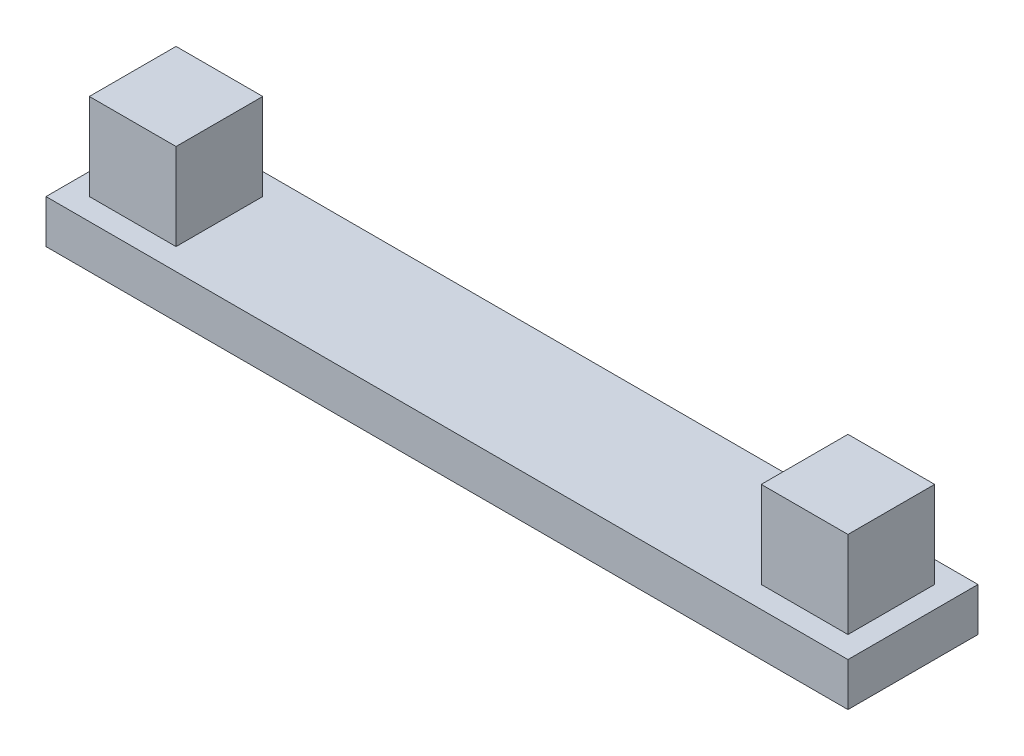
SolidWorks part; units mm, degrees
ref_plane "Front Plane" through (0, 0, 0) normal (0, 0, 1) x (1, 0, 0)
ref_plane "Top Plane" through (0, 0, 0) normal (0, 1, 0) x (1, 0, 0)
ref_plane "Right Plane" through (0, 0, 0) normal (1, 0, 0) x (0, 0, -1)
sketch "Sketch1" plane through (0, 0, 0) normal (0, 1, 0) x (1, 0, 0)
  line L1 (0, 0) -> (18.5, 0)
  line L2 (0, 0) -> (0, 3)
  line L3 (0, 3) -> (18.5, 3)
  line L4 (18.5, 0) -> (18.5, 3)
  line L5 (0, 0) -> (18.5, 3) construction
  line L6 (0, 3) -> (18.5, 0) construction
  line L7 (0.5, 2.5) -> (2.5, 2.5)
  line L8 (0.5, 2.5) -> (0.5, 0.5)
  line L9 (0.5, 0.5) -> (2.5, 0.5)
  line L10 (2.5, 2.5) -> (2.5, 0.5)
  line L11 (0.5, 2.5) -> (2.5, 0.5) construction
  line L12 (0.5, 0.5) -> (2.5, 2.5) construction
  line L13 (16, 2.5) -> (18, 2.5)
  line L14 (16, 2.5) -> (16, 0.5)
  line L15 (16, 0.5) -> (18, 0.5)
  line L16 (18, 2.5) -> (18, 0.5)
  line L17 (16, 2.5) -> (18, 0.5) construction
  line L18 (16, 0.5) -> (18, 2.5) construction
  point P4 (9.25, 1.5)
  point P10 (1.5, 1.5)
  point P15 (17, 1.5)
  point P16 (0, 0)
  point P17 (0, 1.5)
  point P18 (0, 0)
  point P19 (0, 0)
  point P20 (0, 0)
  point P21 (0, 0)
  point P22 (18.5, 1.5)
  dimension "D1" = 18.5
  dimension "D2" = 3
  dimension "D3" = 15.5
  dimension "D4" = 2
  dimension "D5" = 7.75
extrude "Boss-Extrude1" add sketch "Sketch1" along normal blind 1 contours L1 L4 L3 L2 L7 L10 L9 L8 L13 L16 L15 L14 region at (9.25, 0, -1.5)
ref_plane "Plane1" through (2.5, 0, -2.5) normal (1, 0, 0) x (0, 0, -1)
extrude "Boss-Extrude2" add sketch "Sketch1<3>" along normal blind 3 contours L7 L10 L9 L8 | L13 L16 L15 L14
sketch "Sketch1<3>" plane through (0, 0, 0) normal (0, 1, 0) x (1, 0, 0) same geometry as "Sketch1"
